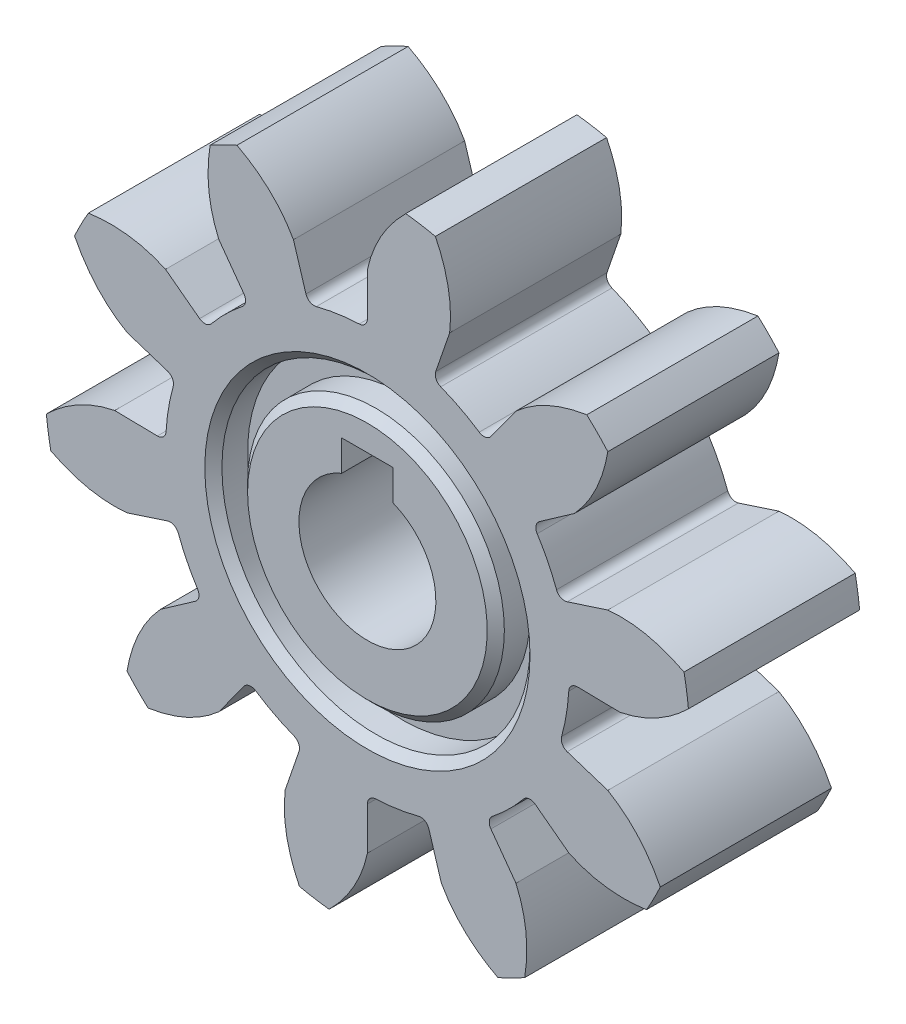
SolidWorks part; units mm, degrees
ref_plane "Front Plane" through (0, 0, 0) normal (0, 0, 1) x (1, 0, 0)
ref_plane "Top Plane" through (0, 0, 0) normal (0, 1, 0) x (1, 0, 0)
ref_plane "Right Plane" through (0, 0, 0) normal (1, 0, 0) x (0, 0, -1)
sketch "Sketch1" plane through (0, 0, 0) normal (0, 0, 1) x (1, 0, 0)
  circle A0 centre (0, 0) radius 18.852
  circle A1 centre (0, 0) radius 15.71
  circle A2 centre (0, 0) radius 14.7626
  circle A3 centre (0, 0) radius 12.568
  circle A4 centre (0, 0) radius 11.7825
  dimension "Root" = 23.565
  dimension "Clearance" = 25.136
  dimension "Base" = 29.5251
  dimension "Pitch" = 31.42
  dimension "Addenum" = 37.704
sketch "Sketch2" plane through (0, 0, 0) normal (0, 0, 1) x (1, 0, 0)
  line L0 (0, 0) -> (0, 14.7626)
  line L1 (0, 0) -> (7.3813, 12.7848) construction
  line L2 (0, 0) -> (12.7848, 7.3813) construction
  line L3 (0, 0) -> (14.7626, 0) construction
  line L4 (14.7626, 0) -> (14.7626, 23.189) construction
  line L5 (12.7848, 7.3813) -> (5.0551, 20.7695) construction
  line L6 (7.3813, 12.7848) -> (0.6872, 16.6496) construction
  line L7 (0, 0) -> (4.8547, 14.9411) construction
  line L8 (0, 0) -> (9.2341, 12.7097)
  line L9 (2.5912, 15.4948) -> (0, 0) construction
  line L10 (4.8031, 13.9594) -> (0, 0)
  circle A2 centre (0, 0) radius 14.7626 construction
  arc A3 (4.5619, 14.04) -> (0, 14.7626) centre (0, 0) ccw
  circle A4 centre (0, 0) radius 15.71 construction
  arc A5 (4.8547, 14.9411) -> (0.2706, 15.7077) centre (0, 0) ccw
  spline S0 degree 3 poles (0, 14.7626) (1.2986, 20.8081) (9.7808, 23.1969) (14.7626, 23.189) knots 0 0 0 0 1 1 1 1
  spline S1 degree 3 poles (4.8031, 13.9594) (5.5421, 20.0984) (-1.7015, 25.117) (-6.4147, 26.7304) knots 0 0 0 0 1 1 1 1
  point P10 (0, 0)
  dimension "D2" = 90
  dimension "D3" = 23.189
  dimension "D4" = 15.4593
  dimension "D5" = 7.7297
  dimension "Circulare pitch" = 36
  dimension "D1" = 4
sketch "Sketch3" plane through (0, 0, 0) normal (0, 0, 1) x (1, 0, 0)
  line L0 (4.8031, 13.9594) -> (0, 0) construction
  line L1 (0, 0) -> (0, 14.7626) construction
  line L2 (4.8031, 13.9594) -> (3.8335, 11.1414)
  line L3 (0, 11.7825) -> (0, 14.7626)
  circle A0 centre (0, 0) radius 11.7825 construction
  circle A1 centre (0, 0) radius 18.852 construction
  arc A2 (3.8335, 11.1414) -> (0, 11.7825) centre (0, 0) ccw
  arc A3 (3.9709, 18.429) -> (2.2411, 18.7183) centre (0, 0) ccw
  spline S0 degree 3 poles (3883.1383, -925.1744) (-4080.4899, 636.3662) (4139.6336, -300.8674) (-3982.4642, 99.0781) knots -6.53892 -6.53892 -6.53892 -6.53892 7.954263 7.954263 7.954263 7.954263 only from (0, 14.7626) to (14.7626, 23.189) construction
  spline S1 degree 3 poles (-3972.8744, 388.5608) (4065.5234, -725.8649) (-4012.293, 1062.3525) (3798.0217, -1202.027) knots -6.53892 -6.53892 -6.53892 -6.53892 7.954263 7.954263 7.954263 7.954263 only from (4.8031, 13.9594) to (-6.4147, 26.7304) construction
  spline S2 degree 3 poles (0, 14.7626) (0.3335, 16.3152) (1.1409, 17.6267) (2.2411, 18.7183) knots 0 0 0 0 0.256831 0.256831 0.256831 0.256831
  spline S3 degree 3 poles (4.8031, 13.9594) (4.9929, 15.5361) (4.6561, 17.0389) (3.9709, 18.429) knots 0 0 0 0 0.256831 0.256831 0.256831 0.256831
extrude "Boss-Extrude1" add sketch "Sketch3" along normal blind 10
ref_axis "Axis1" through (0, 0, 0) along (0, 0, 1)
pattern_circular "CirPattern1" count 10 over 360 about axis through (0, 0, 0) along (0, 0, 1) of bodies 101
extrude "Boss-Extrude2" add sketch "Sketch1" along normal blind 10 contours A4 region at (0, 0, 0)
sketch "Sketch4" plane through (0, 0, 10) normal (0, 0, 1) x (1, 0, 0)
  circle A0 centre (0, 0) radius 9
  circle A1 centre (0, 0) radius 7.5
  circle A2 centre (0, 0) radius 4
  dimension "D1" = 8
  dimension "D2" = 18
  dimension "15" = 15
extrude "Cut-Extrude1" cut sketch "Sketch4" against normal blind 2 contours A0 A1 region at (-8.7454, 0, 10)
extrude "Cut-Extrude2" cut sketch "Sketch4<3>" against normal through all contours A2 region at (0, 0, 10)
sketch "Sketch4<3>" plane through (0, 0, 10) normal (0, 0, 1) x (1, 0, 0) same geometry as "Sketch4"
sketch "Sketch5" plane through (0, 0, 0) normal (0, 0, -1) x (-1, 0, 0)
  circle A1 centre (0, 0) radius 4
  circle A2 centre (0, 0) radius 4
  circle A3 centre (0, 0) radius 7.5
  circle A4 centre (0, 0) radius 7.5
  circle A5 centre (0, 0) radius 9
  circle A6 centre (0, 0) radius 9
  dimension "D1" = 0
  dimension "D2" = 0
  dimension "D3" = 0
extrude "Cut-Extrude3" cut sketch "Sketch5" against normal blind 2 contours A6 A4 region at (8.7454, 0, 0)
fillet "Fillet1" radius 0.5 20 edges at (-3.4474, 11.2669, 5) (-11.2058, 3.641, 5) (-6.9256, 9.5322, 5) (-9.6501, -6.7603, 5) (-11.7808, 0.203, 5) (-9.4115, 7.0888, 5) (0, 11.7825, 5) (6.9256, 9.5322, 5) (-3.8335, -11.1414, 5) (-11.2058, -3.641, 5) (-6.9256, -9.5322, 5) (0, -11.7825, 5) (3.4474, -11.2669, 5) (9.4115, -7.0888, 5) (3.8335, 11.1414, 5) (6.9256, -9.5322, 5) (11.2058, -3.641, 5) (11.7808, -0.203, 5) (11.2058, 3.641, 5) (9.6501, 6.7603, 5)
chamfer "Chamfer1" distance 0.5 angle 45 2 edges at (-7.5, 0, 0) (7.5, 0, 10)
chamfer "Chamfer2" distance 0.5 angle 45 2 edges at (9, 0, 10) (-9, 0, 0)
sketch "Sketch6" plane through (0, 0, 0) normal (0, 0, 1) x (1, 0, 0)
  line L0 (1.5, 4) -> (-1.5, 4) construction
  line L1 (-1.5, 2.5) -> (1.5, 2.5)
  line L2 (-1.5, 2.5) -> (-1.5, 5.5)
  line L3 (-1.5, 5.5) -> (1.5, 5.5)
  line L4 (1.5, 2.5) -> (1.5, 5.5)
  circle A0 centre (0, 0) radius 4 construction
  point P4 (0, 2.5)
  dimension "D1" = 3
  dimension "D2" = 3
extrude "Cut-Extrude4" cut sketch "Sketch6" against normal through all both and the other way through all
equation "\"Module\"= 3.142"
equation "\"No of teeth\"= 10"
equation "\"Pressure angle\"= 20deg"
equation "\"Pitch@Sketch1\"= \"Module\" * \"No of teeth\""
equation "\"Addenum@Sketch1\" = \"Pitch@Sketch1\" + ( \"Module\" * 2 )"
equation "\"Clearance@Sketch1\"= \"Pitch@Sketch1\" - ( \"Module\" * 2 )"
equation "\"Root@Sketch1\"= \"Pitch@Sketch1\" - ( ( \"Module\" * 1.25 ) * 2 )"
equation "\"Base@Sketch1\"= \"Pitch@Sketch1\" * cos ( \"Pressure angle\" )"
equation "\"D3@Sketch2\"= \"Base@Sketch1\" * pi / 4"
equation "\"D4@Sketch2\"=\"D3@Sketch2\"/3*2"
equation "\"D5@Sketch2\"=\"D3@Sketch2\"/3"
equation "\"Circulare pitch@Sketch2\"= 360 / \"No of teeth\""
equation "\"D1@CirPattern1\"=\"No of teeth\""
